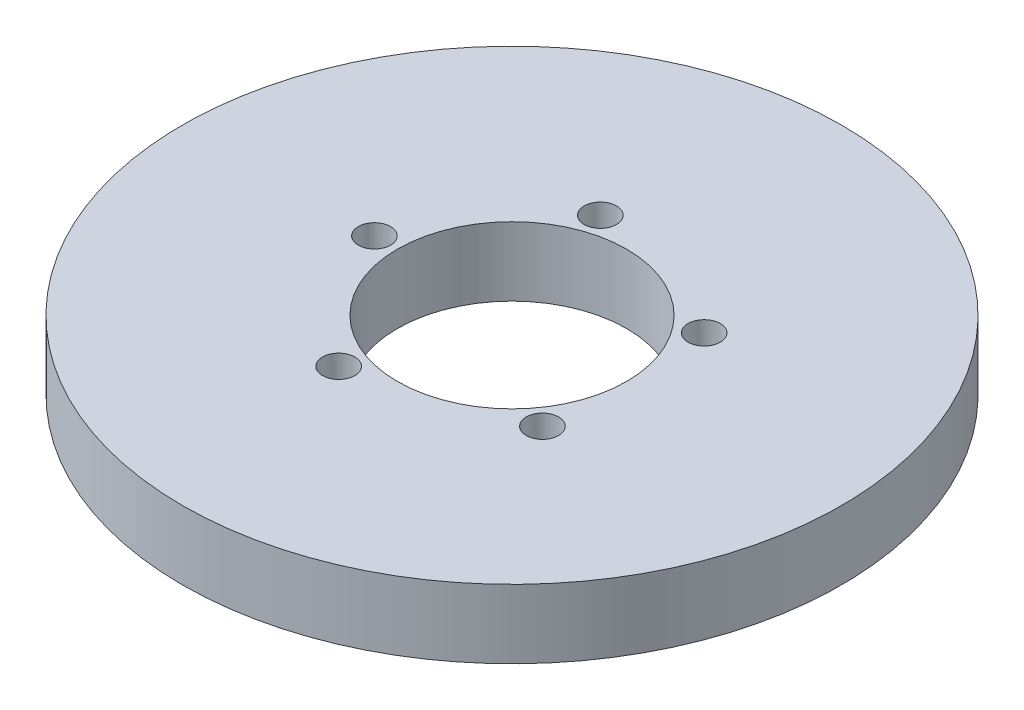
SolidWorks part; units mm, degrees
ref_plane "Front Plane" through (0, 0, 0) normal (0, 0, 1) x (1, 0, 0)
ref_plane "Top Plane" through (0, 0, 0) normal (0, 1, 0) x (1, 0, 0)
ref_plane "Right Plane" through (0, 0, 0) normal (1, 0, 0) x (0, 0, -1)
sketch "Sketch1" plane through (0, 0, 0) normal (0, 1, 0) x (1, 0, 0)
  circle A0 centre (0, 0) radius 57.5
  dimension "FLANGE_OD" = 115
extrude "Boss-Extrude1" add sketch "Sketch1" along normal blind 12
sketch "Sketch2" plane through (0, 0, 0) normal (0, 1, 0) x (1, 0, 0)
  circle A0 centre (0, 0) radius 20
  dimension "BORE_D" = 40
extrude "Cut-Extrude1" cut sketch "Sketch2" along normal through all
sketch "Sketch3" plane through (0, 12, 0) normal (0, 1, 0) x (1, 0, 0)
  circle A0 centre (0, 0) radius 24.0029 construction
  circle A1 centre (-24.0029, 0) radius 2.8176
  dimension "BOLT_D" = 5.6353
  dimension "BOLT_PCD" = 48.0057
extrude "Cut-Extrude2" cut sketch "Sketch3" against normal blind 10.794
pattern_circular "CirPattern1" count 5 over 360 about axis through (0, 0, 0) along (0, 1, 0) of "Cut-Extrude2"
